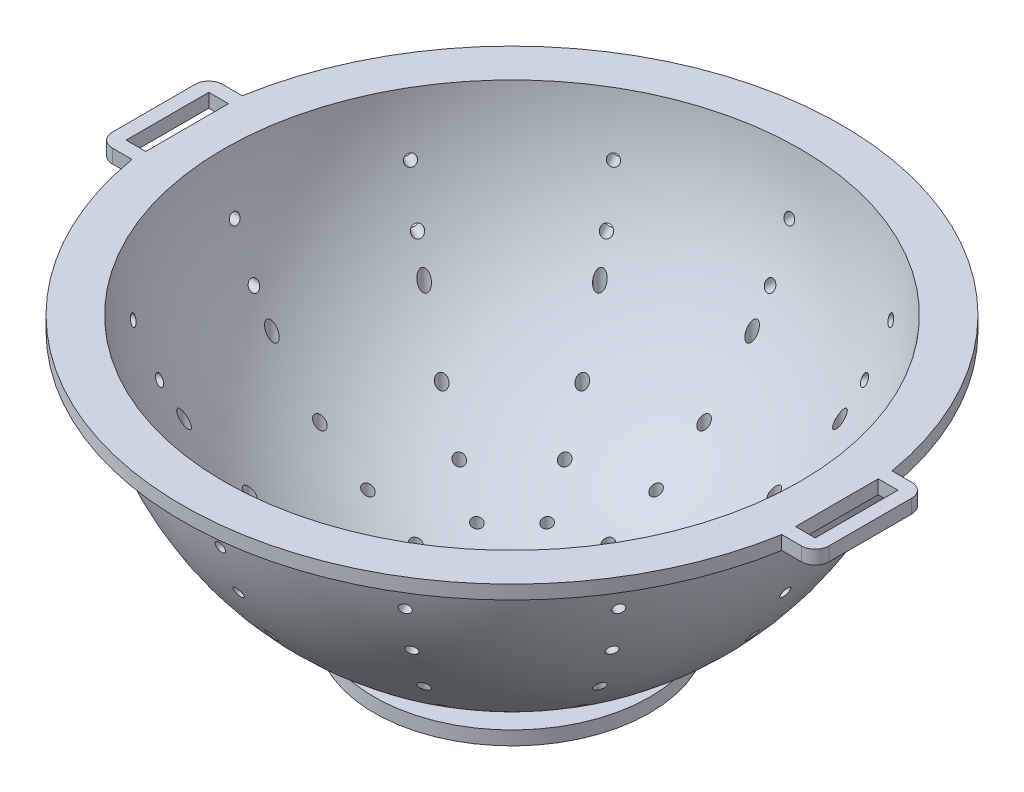
SolidWorks part; units mm, degrees
ref_plane "Front Plane" through (0, 0, 0) normal (0, 0, 1) x (1, 0, 0)
ref_plane "Top Plane" through (0, 0, 0) normal (0, 1, 0) x (1, 0, 0)
ref_plane "Right Plane" through (0, 0, 0) normal (1, 0, 0) x (0, 0, -1)
sketch "Sketch1" plane through (0, 0, 0) normal (0, 0, 1) x (1, 0, 0)
  line L0 (-139.1215, 127) -> (-132.7439, 127)
  line L1 (0, 0) -> (0, 6.35)
  line L2 (0, 0) -> (-63.5, 0)
  line L3 (0, 0) -> (0, 6.35)
  line L4 (0, 6.35) -> (-63.5, 6.35)
  line L5 (-63.5, 0) -> (-63.5, 6.35)
  line L6 (-151.8215, 127) -> (-138.395, 127)
  line L7 (-151.8215, 127) -> (-151.8215, 120.65)
  line L8 (-151.8215, 120.65) -> (-138.395, 120.65)
  line L9 (-138.395, 127) -> (-138.395, 120.65)
  arc A0 (-139.1215, 127) -> (0, 0) centre (0, 139.7) ccw
  arc A1 (-132.7439, 127) -> (0, 6.35) centre (0, 139.7) ccw
  arc A2 (-132.7978, 127.5773) -> (0, 6.35) centre (0, 139.7) ccw construction
  dimension "D1" = 279.4
  dimension "D2" = 127
  dimension "D3" = 6.35
  dimension "D4" = 63.5
  dimension "D5" = 6.35
  dimension "D6" = 12.7
  dimension "D7" = 6.35
revolve "Revolve1" add sketch "Sketch1" angle 360 about L1 region at (-145.3005, 123.7955, 0) region at (-138.6458, 124.8163, 0) region at (-135.5695, 125.164, 0) region at (-44.348, 2.6816, 0) region at (-15.6633, 3.805, 0)
sketch "Sketch2" plane through (0, 127, 0) normal (0, 1, 0) x (1, 0, 0)
  line L1 (158.75, -25.4) -> (-158.75, -25.4)
  line L2 (165.1, -19.05) -> (165.1, 19.05)
  line L3 (158.75, 25.4) -> (-158.75, 25.4)
  line L4 (-165.1, -19.05) -> (-165.1, 19.05)
  line L5 (165.1, -25.4) -> (-165.1, 25.4) construction
  line L6 (165.1, 25.4) -> (-165.1, -25.4) construction
  circle A0 centre (0, 0) radius 151.8215 construction
  circle A1 centre (0, 0) radius 151.8215
  arc A2 (165.1, 19.05) -> (158.75, 25.4) centre (158.75, 19.05) ccw
  arc A3 (158.75, -25.4) -> (165.1, -19.05) centre (158.75, -19.05) ccw
  arc A4 (-158.75, 25.4) -> (-165.1, 19.05) centre (-158.75, 19.05) ccw
  arc A5 (-158.75, -25.4) -> (-165.1, -19.05) centre (-158.75, -19.05) cw
  point P0 (0, 0)
  circle M7 centre (0, 0) radius 151.8215
  dimension "D3" = 6.35
  dimension "D1" = 50.8
  dimension "D2" = 330.2
extrude "Boss-Extrude1" add sketch "Sketch2" against normal up to surface (6.35 mm away) contours L1 A3 L2 A2 L3 M7 | A5 L1 L3 A4 L4 M7 region at (157.9511, 127, 0) region at (-157.9511, 127, 0) up to face at (138.395, 120.65, 0)
sketch "Sketch3" plane through (0, 127, 0) normal (0, 1, 0) x (1, 0, 0)
  line L0 (0, 0) -> (-22.124, 0) construction
  line L1 (-22.124, 0) -> (-44.248, 0) construction
  line L2 (-44.248, 0) -> (-66.3719, 0) construction
  line L3 (-66.3719, 0) -> (-88.4959, 0) construction
  line L4 (-88.4959, 0) -> (-110.6199, 0) construction
  line L5 (-110.6199, 0) -> (-132.7439, 0) construction
  line L58 (-158.75, 19.05) -> (-149.6817, 19.05)
  line L59 (-158.75, -19.05) -> (-158.75, 19.05)
  line L60 (-149.6817, -19.05) -> (-158.75, -19.05)
  line L61 (-158.75, 19.05) -> (-149.6817, 19.05)
  line L62 (-158.75, -19.05) -> (-158.75, 19.05)
  line L63 (-149.6817, -19.05) -> (-158.75, -19.05)
  line L70 (149.6817, -19.05) -> (149.6817, 19.05)
  line L71 (-149.6817, -19.05) -> (-149.6817, 19.05)
  line L73 (149.6817, 19.05) -> (158.75, 19.05)
  line L74 (158.75, 19.05) -> (158.75, -19.05)
  line L75 (158.75, -19.05) -> (149.6817, -19.05)
  line L76 (149.6817, 19.05) -> (158.75, 19.05)
  line L77 (158.75, 19.05) -> (158.75, -19.05)
  line L78 (158.75, -19.05) -> (149.6817, -19.05)
  circle A0 centre (0, 0) radius 132.7439 construction
  circle A1 centre (-95.7996, 55.3099) radius 2.3813
  circle A2 centre (-76.6397, 44.248) radius 2.3813
  circle A3 centre (-57.4798, 33.186) radius 2.3812
  circle A4 centre (-38.3199, 22.124) radius 2.3812
  circle A5 centre (-19.1599, 11.062) radius 2.3813
  circle A6 centre (-55.3099, 95.7996) radius 2.3812
  circle A7 centre (-44.248, 76.6397) radius 2.3812
  circle A8 centre (-33.186, 57.4798) radius 2.3813
  circle A9 centre (-22.124, 38.3199) radius 2.3812
  circle A10 centre (-11.062, 19.1599) radius 2.3813
  circle A11 centre (0, 110.6199) radius 2.3812
  circle A12 centre (0, 88.4959) radius 2.3812
  circle A13 centre (0, 66.3719) radius 2.3812
  circle A14 centre (0, 44.248) radius 2.3812
  circle A15 centre (0, 22.124) radius 2.3813
  circle A16 centre (55.3099, 95.7996) radius 2.3812
  circle A17 centre (44.248, 76.6397) radius 2.3812
  circle A18 centre (33.186, 57.4798) radius 2.3812
  circle A19 centre (22.124, 38.3199) radius 2.3813
  circle A20 centre (11.062, 19.1599) radius 2.3813
  circle A21 centre (95.7996, 55.3099) radius 2.3813
  circle A22 centre (76.6397, 44.248) radius 2.3813
  circle A23 centre (57.4798, 33.186) radius 2.3812
  circle A24 centre (38.3199, 22.124) radius 2.3812
  circle A25 centre (19.1599, 11.062) radius 2.3813
  circle A26 centre (110.6199, 0) radius 2.3813
  circle A27 centre (88.4959, 0) radius 2.3813
  circle A28 centre (66.3719, 0) radius 2.3813
  circle A29 centre (44.248, 0) radius 2.3812
  circle A30 centre (22.124, 0) radius 2.3813
  circle A31 centre (95.7996, -55.3099) radius 2.3813
  circle A32 centre (76.6397, -44.248) radius 2.3813
  circle A33 centre (57.4798, -33.186) radius 2.3812
  circle A34 centre (38.3199, -22.124) radius 2.3812
  circle A35 centre (19.1599, -11.062) radius 2.3813
  circle A36 centre (55.3099, -95.7996) radius 2.3812
  circle A37 centre (44.248, -76.6397) radius 2.3812
  circle A38 centre (33.186, -57.4798) radius 2.3812
  circle A39 centre (22.124, -38.3199) radius 2.3812
  circle A40 centre (11.062, -19.1599) radius 2.3813
  circle A41 centre (0, -110.6199) radius 2.3812
  circle A42 centre (0, -88.4959) radius 2.3812
  circle A43 centre (-22.124, 0) radius 2.3813
  circle A44 centre (-44.248, 0) radius 2.3812
  circle A45 centre (-66.3719, 0) radius 2.3813
  circle A46 centre (-88.4959, 0) radius 2.3813
  circle A47 centre (-110.6199, 0) radius 2.3813
  circle A48 centre (0, -66.3719) radius 2.3812
  circle A49 centre (0, -44.248) radius 2.3812
  circle A50 centre (0, -22.124) radius 2.3813
  circle A51 centre (-55.3099, -95.7996) radius 2.3812
  circle A52 centre (-44.248, -76.6397) radius 2.3812
  circle A53 centre (-33.186, -57.4798) radius 2.3813
  circle A54 centre (-22.124, -38.3199) radius 2.3812
  circle A55 centre (-11.062, -19.1599) radius 2.3813
  circle A56 centre (-95.7996, -55.3099) radius 2.3813
  circle A57 centre (-76.6397, -44.248) radius 2.3813
  circle A58 centre (-57.4798, -33.186) radius 2.3812
  circle A59 centre (-38.3199, -22.124) radius 2.3812
  circle A60 centre (-19.1599, -11.062) radius 2.3813
  dimension "D3" = 4.7625
  dimension "D1" = 6.35
  dimension "D2" = 6.35
  dimension "D4" = 12
extrude "Cut-Extrude2" cut sketch "Sketch3" against normal through all
sketch "Sketch4" plane through (165.1, 0, 0) normal (1, 0, 0) x (0, 0, -1)
  circle A0 centre (0, 79.375) radius 2.3812
  circle A1 centre (0, 101.6) radius 2.3812
  dimension "D1" = 4.7625
  dimension "D2" = 79.375
  dimension "D3" = 22.225
extrude "Cut-Extrude3" cut sketch "Sketch4" against normal up to next
pattern_circular "CirPattern1" count 12 over 360 of "Cut-Extrude3"
